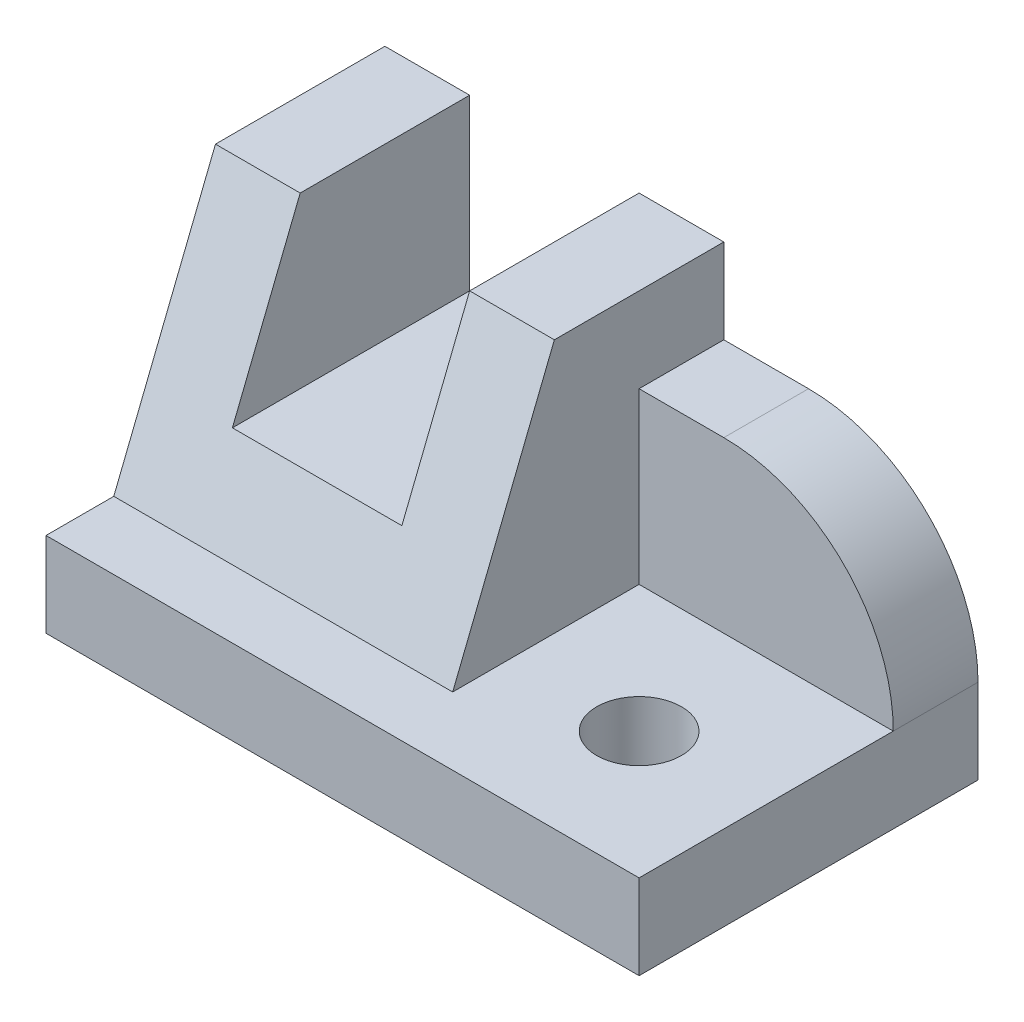
SolidWorks part; units mm, degrees
ref_plane "Front Plane" through (0, 0, 0) normal (0, 0, 1) x (1, 0, 0)
ref_plane "Top Plane" through (0, 0, 0) normal (0, 1, 0) x (1, 0, 0)
ref_plane "Right Plane" through (0, 0, 0) normal (1, 0, 0) x (0, 0, -1)
ref_plane "Plane1" through (0, 0, 0) normal (-1, 0, 0) x (0, -1, 0)
sketch "Sketch1" plane through (0, 0, 0) normal (-1, 0, 0) x (0, -1, 0)
  line L0 (-10, -8) -> (-40, -20)
  line L1 (-40, -20) -> (-10, -20)
  line L2 (-10, -20) -> (-10, -8)
  dimension "D1" = 30
  dimension "Width" = 12
extrude "Boss-Extrude1" add sketch "Sketch1" against normal blind 40
sketch "Sketch2" plane through (0, 0, -20) normal (0, 0, -1) x (-1, 0, 0)
  line L0 (-40, 40) -> (0, 40)
  line L1 (0, 40) -> (0, 10)
  line L2 (0, 10) -> (-40, 10)
  line L3 (-40, 10) -> (-40, 40)
extrude "Boss-Extrude2" add sketch "Sketch2" along normal blind 20
sketch "Sketch3" plane through (40, 0, 0) normal (1, 0, 0) x (0, 0, -1)
  line L0 (40, 10) -> (0, 10)
  line L1 (0, 10) -> (20, 40)
  line L2 (20, 40) -> (40, 40)
  line L3 (40, 40) -> (40, 10)
extrude "Boss-Extrude3" add sketch "Sketch3" along normal blind 30
sketch "Sketch4" plane through (70, 0, 0) normal (1, 0, 0) x (0, 0, -1)
  line L0 (20, 40) -> (0, 10)
  line L1 (0, 10) -> (30, 10)
  line L2 (30, 10) -> (30, 30)
  line L3 (30, 30) -> (40, 30)
  line L4 (40, 30) -> (40, 40)
  line L5 (40, 40) -> (20, 40)
extrude "Cut-Extrude1" cut sketch "Sketch4" against normal blind 30
sketch "Sketch5" plane through (0, 10, 0) normal (0, -1, 0) x (1, 0, 0)
  line L0 (70, 0) -> (70, -40)
  line L1 (70, -40) -> (0, -40)
  line L2 (0, -40) -> (0, 0)
  line L3 (0, 0) -> (70, 0)
extrude "Boss-Extrude4" add sketch "Sketch5" along normal blind 10
sketch "Sketch6" plane through (0, 0, -40) normal (0, 0, -1) x (-1, 0, 0)
  line L0 (-30, 40) -> (-30, 20)
  line L1 (-30, 20) -> (-10, 20)
  line L2 (-10, 20) -> (-10, 40)
  line L3 (-10, 40) -> (-30, 40)
extrude "Cut-Extrude2" cut sketch "Sketch6" against normal through all
hole_wizard "Ø10.0 (10) Diameter Hole1" positions "Sketch8" profile "Sketch7" hole size "Ø10.0" standard "ANSI Metric"
sketch "Sketch8" plane through (0, 0, 0) normal (0, -1, 0) x (-1, 0, 0)
  point P0 (-55, 15)
sketch "Sketch7" plane through (55, 0, -15) normal (1, 0, 0) x (0, 0, -1)
  line L0 (0, 0) -> (0, 40)
  line L1 (0, 40) -> (5, 40)
  line L2 (5, 40) -> (5, 0)
  line L5 (5, 0) -> (0, 0)
  line L11 (0, -6.35) -> (0, 107.95) construction
  dimension "Thru Hole Dia." = 10
  dimension "Thru Hole Depth" = 40
fillet "Fillet1" radius 20 1 edges at (70, 30, -35) tangent propagation no
